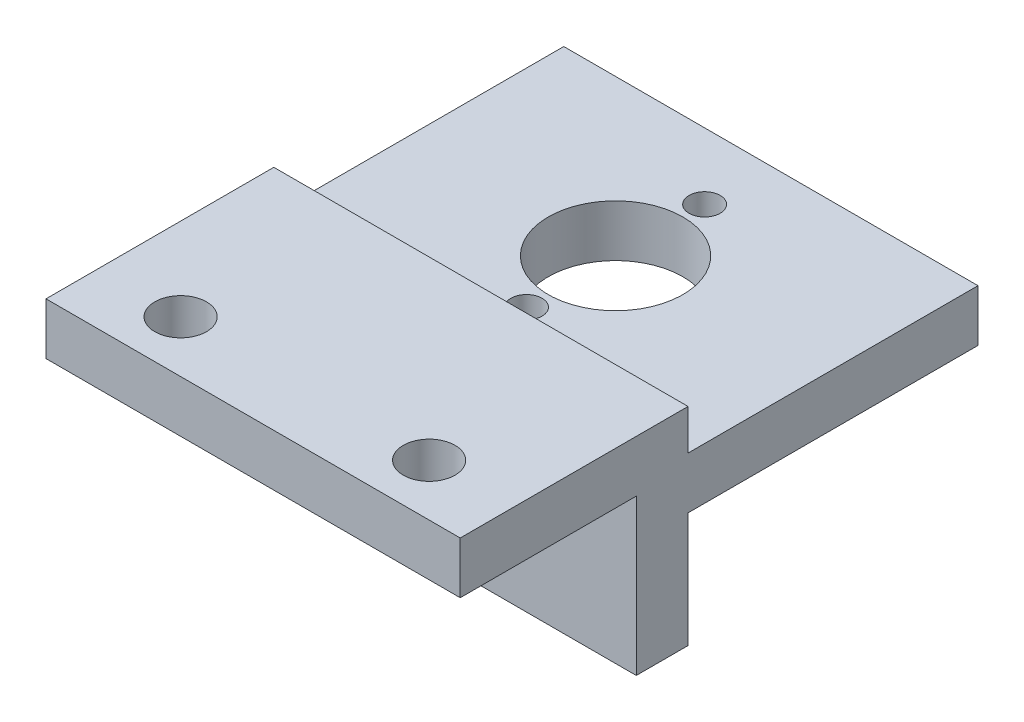
SolidWorks part; units mm, degrees
ref_plane "Front Plane" through (0, 0, 0) normal (0, 0, 1) x (1, 0, 0)
ref_plane "Top Plane" through (0, 0, 0) normal (0, 1, 0) x (1, 0, 0)
ref_plane "Right Plane" through (0, 0, 0) normal (1, 0, 0) x (0, 0, -1)
sketch "Sketch3" plane through (0, 0, 0) normal (0, 1, 0) x (1, 0, 0)
  line L1 (-20, 15) -> (20, 15)
  line L2 (-20, 15) -> (-20, -35)
  line L3 (-20, -35) -> (20, -35)
  line L4 (20, 15) -> (20, -35)
  dimension "D1" = 50
  dimension "D2" = 40
  dimension "D3" = 20
  dimension "D4" = 15
extrude "Boss-Extrude1" add sketch "Sketch3" along normal blind 5
sketch "Sketch6" plane through (0, 5, 0) normal (0, 1, 0) x (1, 0, 0)
  line L0 (-20, 15) -> (-20, -35) construction
  line L1 (-20, -35) -> (20, -35) construction
  circle A0 centre (-12, -30) radius 2.5
  circle A1 centre (12, -30) radius 2.5
  dimension "D1" = 5
  dimension "D4" = 5
  dimension "D2" = 8
  dimension "D3" = 5
  dimension "D5" = 24
  dimension "D9" = 5
extrude "Cut-Extrude6" cut sketch "Sketch6" against normal through all
sketch "Sketch7" plane through (0, 0, 0) normal (0, -1, 0) x (1, 0, 0)
  line L0 (20, 35) -> (20, -15) construction
  line L1 (20, 18) -> (-20, 18)
  line L2 (20, 18) -> (20, 13)
  line L3 (20, 13) -> (-20, 13)
  line L4 (-20, 18) -> (-20, 13)
  line L5 (-20, -15) -> (-20, 35) construction
  line L6 (-20, 35) -> (20, 35) construction
  dimension "D1" = 5
  dimension "D2" = 17
extrude "Boss-Extrude2" add sketch "Sketch7" along normal blind 15
sketch "Sketch8" plane through (0, 0, 0) normal (0, -1, 0) x (1, 0, 0)
  line L0 (20, -15) -> (-20, -15) construction
  line L1 (-20, 13) -> (20, 13)
  line L2 (-20, 13) -> (-20, -15)
  line L3 (-20, -15) -> (20, -15)
  line L4 (20, 13) -> (20, -15)
extrude "Boss-Extrude3" add sketch "Sketch8" along normal blind 3.9
sketch "Sketch1" plane through (0, 0, 0) normal (0, 1, 0) x (1, 0, 0)
  circle A0 centre (0, 0) radius 6.5
  circle A1 centre (0, 8.6) radius 1.5
  circle A2 centre (0, -8.6) radius 1.5
  dimension "D1" = 13
  dimension "D5" = 8.6
  dimension "D2" = 3
  dimension "D3" = 3
  dimension "D4" = 17.2
extrude "Cut-Extrude3" cut sketch "Sketch1" along normal through all both and the other way through all
sketch "Sketch9" plane through (-20, 0, 0) normal (-1, 0, 0) x (0, 0, 1)
  line L1 (-15, 5) -> (13, 5)
  line L2 (-15, 5) -> (-15, 1.1)
  line L3 (-15, 1.1) -> (13, 1.1)
  line L4 (13, 5) -> (13, 1.1)
  dimension "D1" = 3.9
extrude "Cut-Extrude7" cut sketch "Sketch9" against normal up to surface (40 mm away) up to face at (20, -3.475, 12.75)
